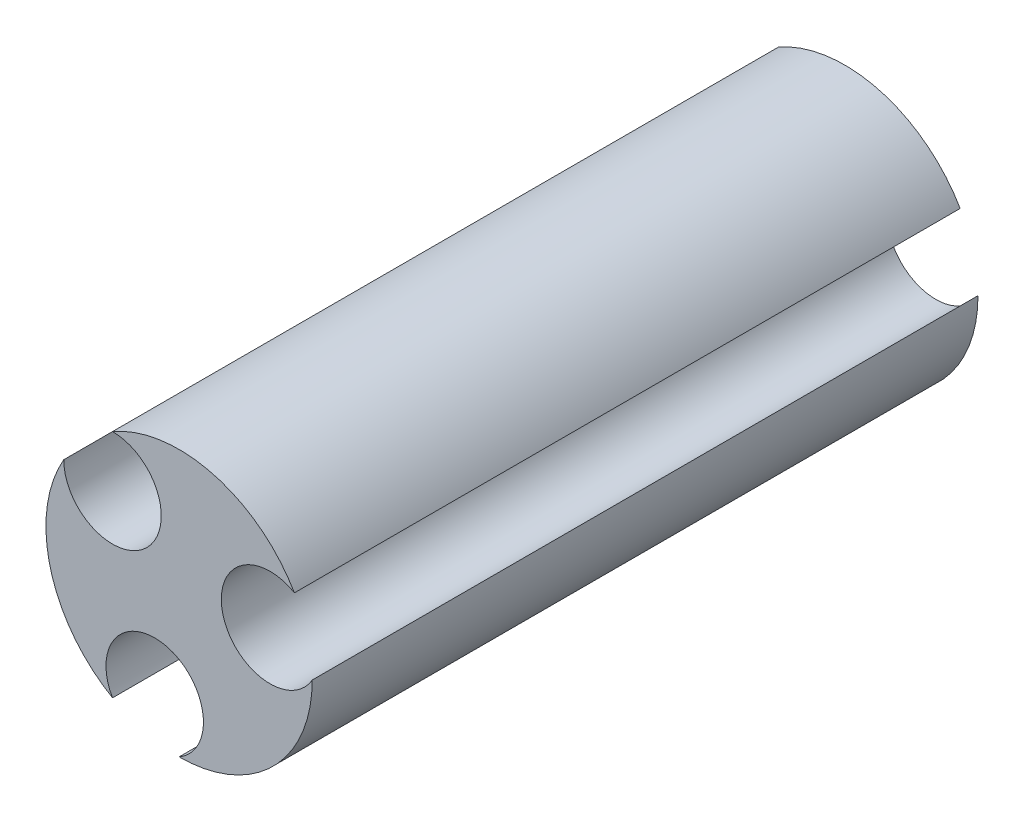
SolidWorks part; units mm, degrees
ref_plane "Front Plane" through (0, 0, 0) normal (0, 0, 1) x (1, 0, 0)
ref_plane "Top Plane" through (0, 0, 0) normal (0, 1, 0) x (1, 0, 0)
ref_plane "Right Plane" through (0, 0, 0) normal (1, 0, 0) x (0, 0, -1)
sketch "Sketch2" plane through (0, 0, 0) normal (0, 0, 1) x (1, 0, 0)
  arc A0 (-1.7321, 1) -> (-1, -1.7321) centre (0, 0) ccw
  arc A1 (1.7321, 1) -> (-1, 1.7321) centre (0, 0) ccw
  arc A2 (-1, -1.7321) -> (0, -2) centre (-0.366, -1.366) cw
  arc A3 (2, 0) -> (1.7321, 1) centre (1.366, 0.366) cw
  arc A4 (-1, 1.7321) -> (-1.7321, 1) centre (-1, 1) cw
  arc A6 (0, -2) -> (2, 0) centre (0, 0) ccw
extrude "Boss-Extrude1" add sketch "Sketch2" along normal blind 10
